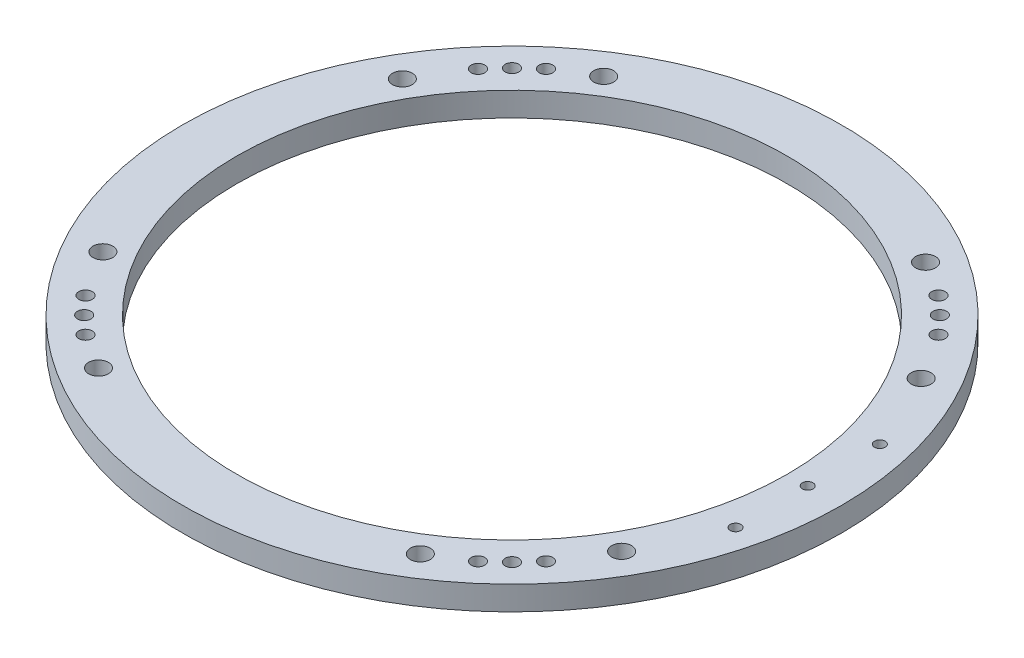
SolidWorks part; units mm, degrees
material "Oak"
ref_plane "Front Plane" through (0, 0, 0) normal (0, 0, 1) x (1, 0, 0)
ref_plane "Top Plane" through (0, 0, 0) normal (0, 1, 0) x (1, 0, 0)
ref_plane "Right Plane" through (0, 0, 0) normal (1, 0, 0) x (0, 0, -1)
sketch "Sketch1" plane through (0, 0, 0) normal (0, 0, 1) x (1, 0, 0)
  line L0 (0, 1125.8152) -> (0, -48874.1848) construction
  line L1 (145.5262, 1052.195) -> (152.4, 1052.195)
  line L9 (145.5262, 1064.895) -> (174.1012, 1064.895)
  line L10 (145.5262, 1064.895) -> (145.5262, 1052.195)
  line L11 (145.5262, 1052.195) -> (174.1012, 1052.195)
  line L12 (174.1012, 1064.895) -> (174.1012, 1052.195)
revolve "Revolve1" add sketch "Sketch1" angle 360 about L0 region at (159.8137, 1058.545, 0)
hole_wizard "9/32 (0.28125) Diameter Hole1" positions "Sketch9" profile "Sketch10" hole size "9/32" standard "ANSI Inch" end condition through all
sketch "Sketch9" plane through (0, 1052.195, 0) normal (0, -1, 0) x (-1, 0, 0)
  line L0 (0, 0) -> (113.0054, 113.0054) construction
  line L3 (0, 0) -> (103.6677, 121.6282) construction
  arc A0 (103.6677, 121.6282) -> (121.6282, 103.6677) centre (0, 0) cw
  circle A1 centre (0, 0) radius 159.8137 construction
  point P0 (103.6677, 121.6282)
  point P2 (121.6282, 103.6677)
  point P15 (113.0054, 113.0054)
sketch "Sketch10" plane through (-103.6677, 1052.195, -121.6282) normal (1, 0, 0) x (0, 0, -1)
  line L0 (0, 0) -> (0, 12.7)
  line L1 (0, 12.7) -> (3.5719, 12.7)
  line L2 (3.5719, 12.7) -> (3.5719, 0)
  line L5 (3.5719, 0) -> (0, 0)
  line L11 (0, -6.35) -> (0, 107.95) construction
  dimension "Thru Hole Dia." = 7.1437
  dimension "Thru Hole Depth" = 12.7
pattern_circular "CirPattern1" count 4 over 360 about axis through (0, 1125.8152, 0) along (0, 1, 0) of "9/32 (0.28125) Diameter Hole1"
ref_plane "Plane1" through (0, 1058.545, 0) normal (0, 1, 0) x (1, 0, 0)
hole_wizard "#10 Clearance Hole1" positions "Sketch14" profile "Sketch15" hole size "#10" standard "ANSI Inch" end condition through all
sketch "Sketch14" plane through (0, 1064.895, 0) normal (0, 1, 0) x (1, 0, 0)
  point P0 (156.21, 38.1)
  point P3 (156.21, 0)
  point P6 (156.21, -38.1)
sketch "Sketch15" plane through (156.21, 1064.895, -38.1) normal (1, 0, 0) x (0, 0, 1)
  line L0 (0, 0) -> (0, 12.7)
  line L1 (0, 12.7) -> (2.8067, 12.7)
  line L2 (2.8067, 12.7) -> (2.8067, 0)
  line L5 (2.8067, 0) -> (0, 0)
  line L11 (0, -6.35) -> (0, 107.95) construction
  dimension "Thru Hole Dia." = 5.6134
  dimension "Thru Hole Depth" = 12.7
hole_wizard "Z (0.413) Diameter Hole1" positions "Sketch16" profile "Sketch17" hole size "Z" standard "ANSI Inch" end condition through all
sketch "Sketch16" plane through (0, 1064.895, 0) normal (0, 1, 0) x (1, 0, 0)
  line L0 (-137.0279, -79.1131) -> (137.0279, 79.1131) construction
  line L4 (137.0279, -79.1131) -> (-137.0279, 79.1131) construction
  line L6 (0, 0) -> (0, 158.2262) construction
  line L8 (-85.0149, -133.4467) -> (85.0149, 133.4467) construction
  line L11 (-85.0149, 133.4467) -> (85.0149, -133.4467) construction
  circle A0 centre (0, 0) radius 158.2262 construction
  circle A1 centre (0, 0) radius 145.5262 construction
  point P0 (-137.0279, -79.1131)
  point P2 (137.0279, -79.1131)
  point P4 (137.0279, 79.1131)
  point P6 (-137.0279, 79.1131)
  point P37 (-85.0149, 133.4467)
  point P39 (85.0149, 133.4467)
  point P41 (85.0149, -133.4467)
  point P43 (-85.0149, -133.4467)
  dimension "D2" = 12.7
  dimension "D1" = 120
  dimension "D3" = 65
sketch "Sketch17" plane through (-137.0279, 1064.895, 79.1131) normal (1, 0, 0) x (0, 0, 1)
  line L0 (0, 0) -> (0, 12.7)
  line L1 (0, 12.7) -> (5.2451, 12.7)
  line L2 (5.2451, 12.7) -> (5.2451, 0)
  line L5 (5.2451, 0) -> (0, 0)
  line L11 (0, -6.35) -> (0, 107.95) construction
  dimension "Thru Hole Dia." = 10.4902
  dimension "Thru Hole Depth" = 12.7
